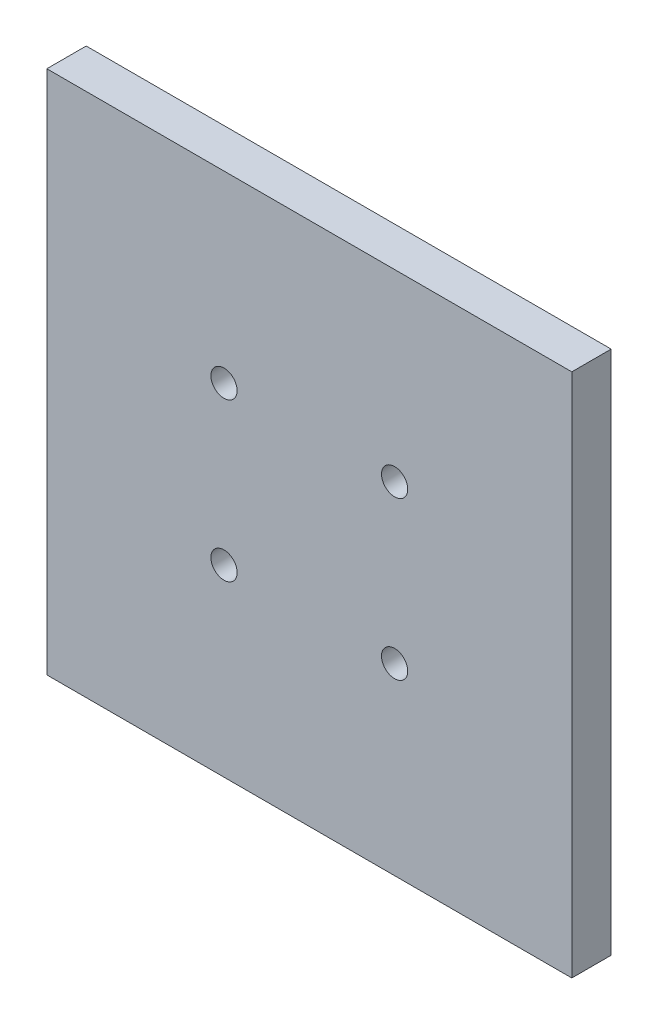
SolidWorks part; units mm, degrees
material "ABS"
ref_plane "Alzado" through (0, 0, 0) normal (0, 0, 1) x (1, 0, 0)
ref_plane "Planta" through (0, 0, 0) normal (0, 1, 0) x (1, 0, 0)
ref_plane "Vista lateral" through (0, 0, 0) normal (1, 0, 0) x (0, 0, -1)
sketch "Sketch1" plane through (0, 0, 0) normal (0, 0, 1) x (1, 0, 0)
  line L0 (0, -1000) -> (0, 49000) construction
  line L5 (-1000, 0) -> (49000, 0) construction
  line L7 (-20, -20) -> (20, -20)
  line L8 (-20, -20) -> (-20, 20)
  line L9 (-20, 20) -> (20, 20)
  line L10 (20, -20) -> (20, 20)
  line L11 (-20, -20) -> (20, 20) construction
  line L12 (-20, 20) -> (20, -20) construction
  circle A0 centre (6.5, -6) radius 1
  circle A1 centre (-6.5, -6) radius 1
  circle A2 centre (6.5, 6) radius 1
  circle A3 centre (-6.5, 6) radius 1
  point P14 (0, 0)
  dimension "D3" = 2
  dimension "D1" = 6
  dimension "D2" = 6.5
  dimension "D4" = 40
  dimension "D5" = 40
extrude "Boss-Extrude1" add sketch "Sketch1" along normal blind 3
